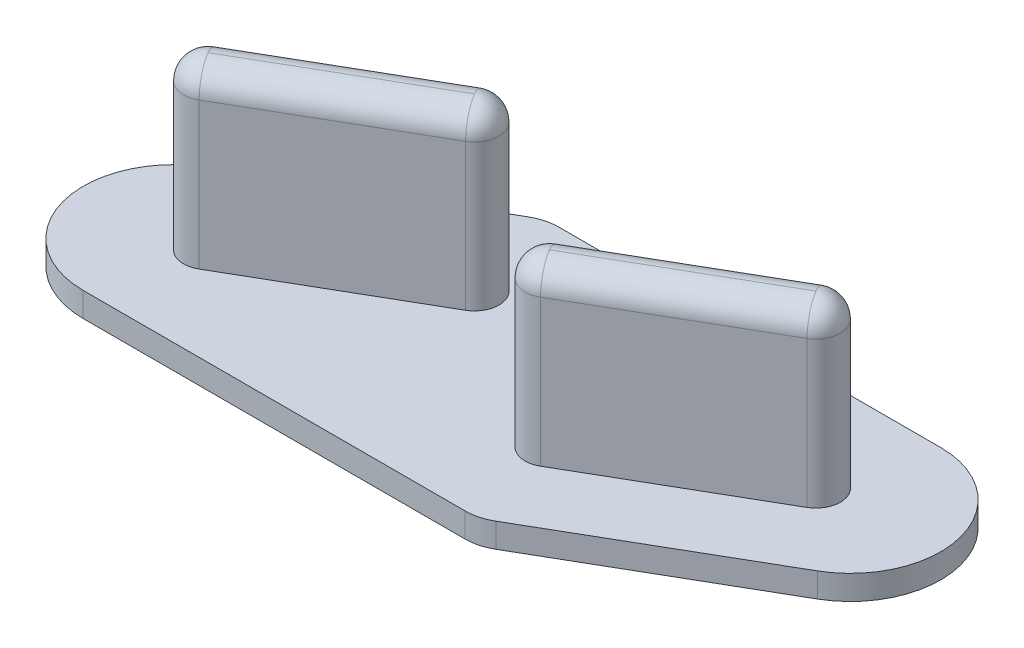
SolidWorks part; units mm, degrees
ref_plane "Front Plane" through (0, 0, 0) normal (0, 0, 1) x (1, 0, 0)
ref_plane "Top Plane" through (0, 0, 0) normal (0, 1, 0) x (1, 0, 0)
ref_plane "Right Plane" through (0, 0, 0) normal (1, 0, 0) x (0, 0, -1)
sketch "Sketch1" plane through (0, 0, 0) normal (0, 1, 0) x (1, 0, 0)
  line L0 (0, -3.7013) -> (15.6506, -3.7013)
  line L1 (16.6506, -3.4334) -> (25.0083, 1.3919)
  line L2 (23.1576, 8.2987) -> (7.507, 8.2987)
  line L3 (6.507, 8.0307) -> (-1.8507, 3.2054)
  line L4 (-3.5752, -0.958) -> (26.7328, 5.5553) construction
  arc A0 (-1.8507, 3.2054) -> (0, -3.7013) centre (0, 0) ccw
  arc A1 (25.0083, 1.3919) -> (23.1576, 8.2987) centre (23.1576, 4.5974) ccw
  arc A2 (15.6506, -3.7013) -> (16.6506, -3.4334) centre (15.6506, -1.7013) ccw
  arc A3 (7.507, 8.2987) -> (6.507, 8.0307) centre (7.507, 6.2987) ccw
  point P17 (6.9711, 8.2987)
  dimension "D4" = 31
  dimension "D5" = 2
  dimension "D1" = 12
  dimension "D2" = 15
  dimension "D3" = 30
extrude "Boss-Extrude1" add sketch "Sketch1" along normal blind 1
sketch "Sketch2" plane through (0, 1, 0) normal (0, 1, 0) x (1, 0, 0)
  line L0 (15.1147, 0.2987) -> (22.0429, 4.2987) construction
  line L1 (14.6147, 1.1647) -> (21.5429, 5.1647)
  line L2 (15.6147, -0.5673) -> (22.5429, 3.4327)
  line L3 (16.6506, -3.4334) -> (25.0083, 1.3919) construction
  line L4 (16.6506, -3.4334) -> (25.0083, 1.3919) construction
  line L5 (18.5788, 8.2987) -> (18.5788, -3.7013) construction
  line L6 (23.1576, 8.2987) -> (7.507, 8.2987) construction
  arc A0 (14.6147, 1.1647) -> (15.6147, -0.5673) centre (15.1147, 0.2987) ccw
  arc A1 (22.5429, 3.4327) -> (21.5429, 5.1647) centre (22.0429, 4.2987) ccw
  arc A2 (25.0083, 1.3919) -> (23.1576, 8.2987) centre (23.1576, 4.5974) ccw construction
  arc A3 (25.0083, 1.3919) -> (23.1576, 8.2987) centre (23.1576, 4.5974) ccw
  point P2 (18.5788, 2.2987)
  point P9 (14.2487, -0.2013)
  point P10 (22.9089, 4.7987)
  point P18 (18.5788, 2.2987)
  dimension "D3" = 10
  dimension "D1" = 4
  dimension "D2" = 2
extrude "Boss-Extrude2" add sketch "Sketch2" along normal blind 7 contours L2 A1 L1 A0 region at (18.5788, 1, -2.2987)
pattern_linear "LPattern1" count 2 spacing 14 along (-1, 0, 0) of "Boss-Extrude2"
fillet "Fillet3" radius 1 8 edges at (14.2487, 8, 0.2013) (18.0788, 8, -3.1647) (22.9089, 8, -4.7987) (19.0788, 8, -1.4327) (0.2487, 8, 0.2013) (4.0788, 8, -3.1647) (8.9089, 8, -4.7987) (5.0788, 8, -1.4327)
sketch "Sketch3" plane through (0, 1, 0) normal (0, 1, 0) x (1, 0, 0)
  line L0 (23.1576, 8.2987) -> (7.507, 8.2987) construction
  circle A0 centre (13.4894, 6.2987) radius 1
  arc A1 (7.507, 8.2987) -> (6.507, 8.0307) centre (7.507, 6.2987) ccw construction
  point P4 (0, 0)
  point P5 (0, 0)
  point P6 (8.4219, 12.3604)
  point P10 (6.9894, 8.2305)
  dimension "D1" = 2
  dimension "D2" = 2
  dimension "D3" = 6.5
extrude "Cut-Extrude1" cut sketch "Sketch3" against normal through all
